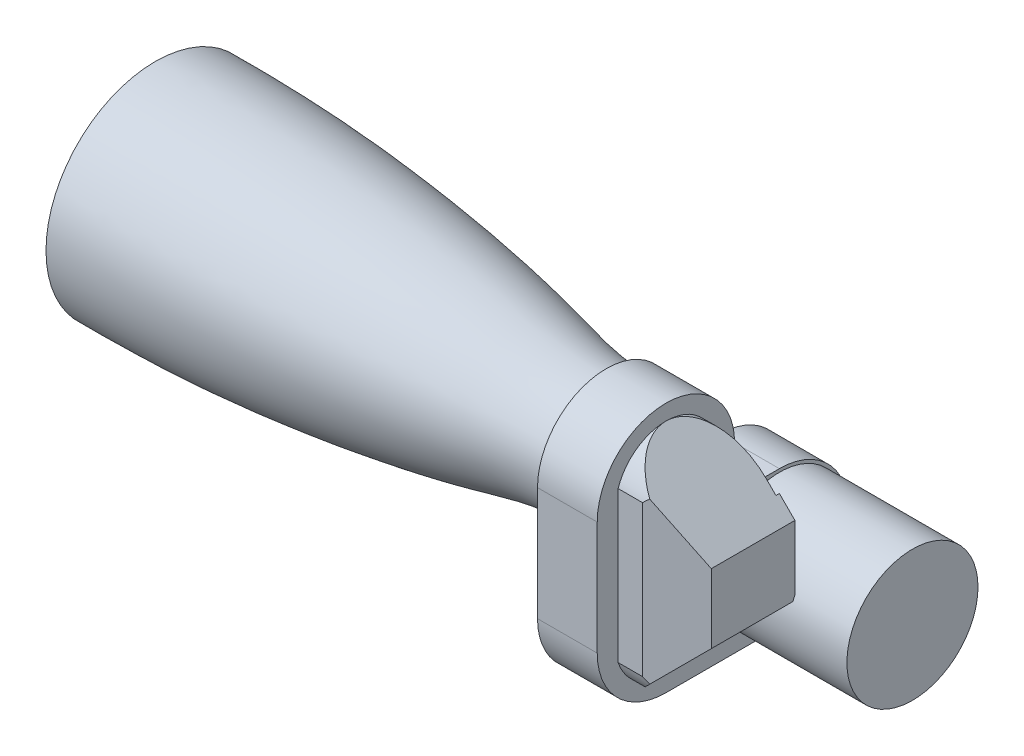
SolidWorks part; units mm, degrees
ref_plane "Front Plane" through (0, 0, 0) normal (0, 0, 1) x (1, 0, 0)
ref_plane "Top Plane" through (0, 0, 0) normal (0, 1, 0) x (1, 0, 0)
ref_plane "Right Plane" through (0, 0, 0) normal (1, 0, 0) x (0, 0, -1)
sketch "Sketch1" plane through (0, 0, 0) normal (0, 1, 0) x (1, 0, 0)
  line L0 (0, 0) -> (75.5, 0) construction
  line L1 (75.5, 0) -> (75.5, 10)
  line L2 (0, 0) -> (0, 18.3)
  line L3 (0, 18.3) -> (-23.3639, 18.3) construction
  line L4 (75.5, 10) -> (97.8461, 10) construction
  line L5 (0, 0) -> (75.5, 0)
  spline S0 degree 3 poles (0, 18.3) (9.7407, 18.3) (26.9901, 17.7429) (54.8823, 14.0808) (69.7771, 10) (75.5, 10) knots 0 0 0 0 0.316328 0.808813 1 1 1 1
  dimension "D1" = 18.3
  dimension "D2" = 10
  dimension "D3" = 75.5
revolve "Revolve1" add sketch "Sketch1" angle 360 about L5
sketch "Sketch2" plane through (75.5, 0, 0) normal (1, 0, 0) x (0, 0, -1)
  line L0 (0, -19) -> (0, 0) construction
  line L1 (19, -19) -> (0, -19) construction
  line L2 (-11.5, 0) -> (-11.5, -19)
  line L3 (11.5, 0) -> (11.5, -7.5)
  line L4 (19, -7.5) -> (11.5, -7.5)
  line L5 (19, -30.5) -> (0, -30.5)
  arc A0 (11.5, 0) -> (-11.5, 0) centre (0, 0) ccw
  arc A2 (-11.5, -19) -> (0, -30.5) centre (0, -19) ccw
  arc A3 (19, -30.5) -> (19, -7.5) centre (19, -19) ccw
  point P1 (0, 11.5)
  dimension "D2" = 23
  dimension "D3" = 42
extrude "Boss-Extrude1" add sketch "Sketch2" along normal blind 10 contours A2 L5 A3 L4 L3 A0 L2
sketch "Sketch3" plane through (0, 0, 11.5) normal (0, 0, 1) x (1, 0, 0)
  line L0 (85.5, -27.9) -> (98.1, -15.3)
  line L1 (98.1, -15.3) -> (98.1, -3.7)
  line L2 (98.1, -3.7) -> (85.5, 8.9)
  line L3 (85.5, 8.9) -> (85.5, -27.9)
  line L4 (85.5, 0) -> (85.5, -19) construction
  point P13 (85.5, -9.5)
  dimension "D1" = 36.8
  dimension "D2" = 12.6
extrude "Boss-Extrude2" add sketch "Sketch3" against normal blind 17 from offset 3.5 contours L1 L2 L3 L0 offset against normal yes
sketch "Sketch4" plane through (0, -30.5, 0) normal (0, -1, 0) x (-1, 0, 0)
  line L0 (-75.5, -6.491) -> (-61.8543, 7.1547)
  line L1 (-75.5, 19) -> (-75.5, 0) construction
  line L2 (-61.8543, 7.1547) -> (-61.8543, 15.8561)
  line L3 (-61.8543, 15.8561) -> (-75.5, 29.5018)
  line L4 (-75.5, 29.5018) -> (-75.5, -6.491)
extrude "Boss-Extrude3" add sketch "Sketch4" against normal blind 10 from offset 5 offset against normal yes
sketch "Sketch6" plane through (85.5, 0, 0) normal (1, 0, 0) x (0, 0, -1)
  line L0 (0, 0.4765) -> (0, -19.4765) construction
  line L1 (8.4235, 0.4765) -> (8.4235, -19.4765)
  line L2 (-8.4235, 0.4765) -> (-8.4235, -19.4765)
  line L3 (9, -27.9) -> (-7.2829, -27.9) construction
  line L4 (7.2829, 8.9) -> (-7.2829, 8.9) construction
  arc A0 (8.4235, 0.4765) -> (-8.4235, 0.4765) centre (0, 0.4765) ccw
  arc A1 (-8.4235, -19.4765) -> (8.4235, -19.4765) centre (0, -19.4765) ccw
  point P3 (0, -9.5)
  point P12 (0, 0)
  point P13 (0, 0)
  dimension "D1" = 16.847
extrude "Cut-Extrude1" cut sketch "Sketch6" along normal blind 10 flip side to cut
sketch "Sketch5" plane through (85.5, 0, 0) normal (1, 0, 0) x (0, 0, -1)
  circle A0 centre (19, -19) radius 10.975
  arc A1 (19, -30.5) -> (19, -7.5) centre (19, -19) ccw construction
  dimension "D1" = 21.95
extrude "Boss-Extrude4" add sketch "Sketch5" along normal blind 22.28 contours A0
chamfer "Chamfer1" [suppressed] distance 8.5 angle 57.296
chamfer "Chamfer2" distance 3 distance2 8.5 1 edges at (98.1, -9.5, 8) first distance on face at (98.1, -10.4949, -2.1318)
